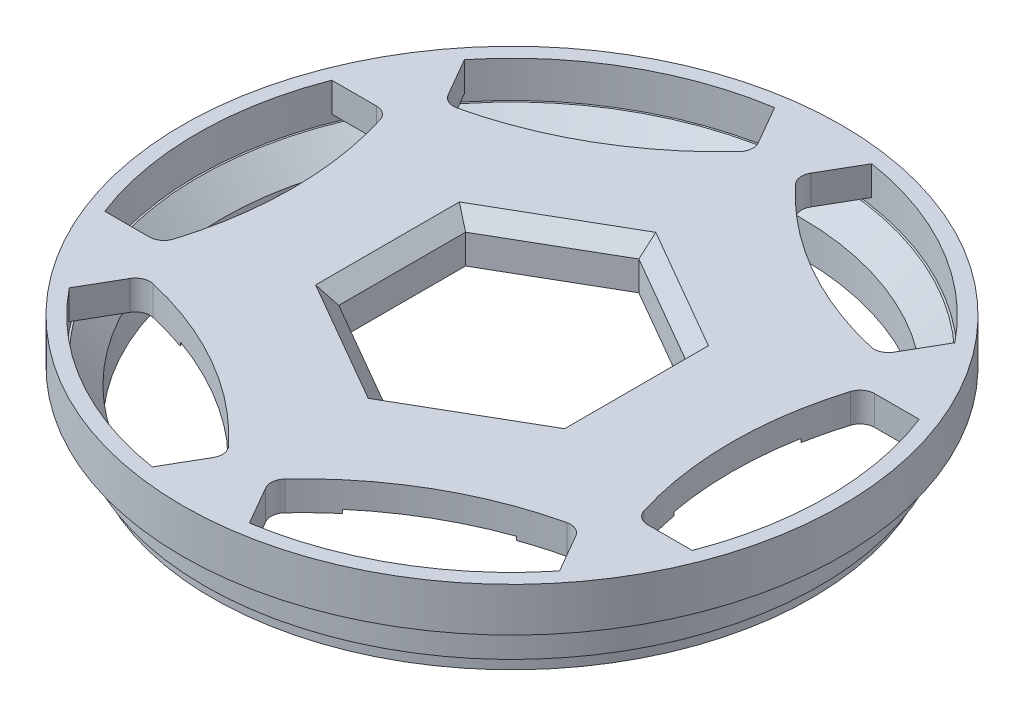
SolidWorks part; units mm, degrees
ref_plane "Ebene vorne" through (0, 0, 0) normal (0, 0, 1) x (1, 0, 0)
ref_plane "Ebene oben" through (0, 0, 0) normal (0, 1, 0) x (1, 0, 0)
ref_plane "Ebene rechts" through (0, 0, 0) normal (1, 0, 0) x (0, 0, -1)
sketch "Skizze1" plane through (0, 0, 0) normal (0, 1, 0) x (1, 0, 0)
  circle A0 centre (0, 0) radius 44
  dimension "D1" = 88
extrude "Aufsatz-Linear austragen1" add sketch "Skizze1" along normal blind 4
sketch "Skizze2" plane through (0, 4, 0) normal (0, 1, 0) x (1, 0, 0)
  line L0 (-32.5715, 15.5) -> (-71.0776, 15.5)
  line L1 (-32.5715, -15.5) -> (-71.0776, -15.5)
  line L2 (-71.0776, 15.5) -> (-71.0776, -15.5)
  circle A0 centre (-78, 0) radius 48
  circle M2 centre (0, 0) radius 44
  dimension "D1" = 78
  dimension "D2" = 96
  dimension "D3" = 31
  dimension "D4" = 15.5
extrude "Schnitt-Linear austragen2" cut sketch "Skizze2" against normal blind 10 contours L1 A0 L0 M2 region at (-36.9648, 4, 0)
sketch "Skizze4" plane through (0, 4, 0) normal (0, 1, 0) x (1, 0, 0)
  circle A0 centre (0, 0) radius 21.0071
pattern_circular "Kreismuster1" count 6 over 360 about axis through (0, 0, 0) along (0, 1, 0) of "Schnitt-Linear austragen2"
sketch "Skizze3" plane through (0, 0, 0) normal (0, -1, 0) x (1, 0, 0)
  line L1 (15, 8.6603) -> (0, 17.3205)
  line L2 (0, 17.3205) -> (-15, 8.6603)
  line L3 (-15, 8.6603) -> (-15, -8.6603)
  line L4 (-15, -8.6603) -> (0, -17.3205)
  line L5 (0, -17.3205) -> (15, -8.6603)
  line L6 (15, -8.6603) -> (15, 8.6603)
  circle A0 centre (0, 0) radius 15 construction
extrude "Schnitt-Linear austragen3" cut sketch "Skizze3" against normal blind 10 and the other way blind 4
fillet "Verrundung1" radius 2 12 edges at (-32.5715, 2, 15.5) (-2.8623, 2, 35.9577) (2.8623, 2, 35.9577) (29.7091, 2, 20.4577) (32.5715, 2, 15.5) (32.5715, 2, -15.5) (29.7091, 2, -20.4577) (2.8623, 2, -35.9577) (-2.8623, 2, -35.9577) (-29.7091, 2, -20.4577) (-32.5715, 2, -15.5) (-29.7091, 2, 20.4577)
sketch "Skizze5" plane through (13.4234, 0, 7.75) normal (-0.866, 0, -0.5) x (-0.5, 0, 0.866)
  line L0 (-34.0256, 0) -> (-41.1795, 0) construction
  circle A0 centre (-39, 0) radius 1.6
sketch "Skizze6" plane through (0, 0, -15.5) normal (0, 0, 1) x (1, 0, 0)
  line L0 (34.0256, 0) -> (41.1795, 0) construction
  circle A0 centre (39, 0) radius 1.6
sketch "Skizze7" plane through (0, 0, 0) normal (0, -1, 0) x (1, 0, 0)
  circle A0 centre (0, 0) radius 32
extrude "Schnitt-Linear austragen7" cut sketch "Skizze7" against normal blind 0.5
sketch "Skizze8" plane through (0, 4, 0) normal (0, 1, 0) x (1, 0, 0)
  circle A0 centre (0, 0) radius 45
  circle A1 centre (0, 0) radius 43
extrude "Aufsatz-Linear austragen2" add sketch "Skizze8" against normal blind 5
sketch "Skizze9" plane through (0, -1, 0) normal (0, -1, 0) x (1, 0, 0)
  circle A0 centre (0, 0) radius 45
  circle A1 centre (0, 0) radius 39.5
extrude "Aufsatz-Linear austragen3" add sketch "Skizze9" along normal blind 8 separate body
extrude "Aufsatz-Linear austragen8" add sketch "Skizze4" against normal blind 6
chamfer "Fase1" distance 3.25 angle 45 1 edges at (0, -1, -39.5)
sketch "Skizze10" plane through (0, -9, 0) normal (0, -1, 0) x (1, 0, 0)
  circle A0 centre (0, 0) radius 42
  circle A1 centre (0, 0) radius 50
extrude "Schnitt-Linear austragen9" cut sketch "Skizze10" against normal blind 7 contours A1 | A0
sketch "Skizze11" plane through (0, -9, 0) normal (0, -1, 0) x (1, 0, 0)
  circle A0 centre (0, 0) radius 40.9
  circle A1 centre (-1.9486, 1.7726) radius 50
extrude "Schnitt-Linear austragen10" cut sketch "Skizze11" against normal blind 2
extrude "Schnitt-Linear austragen11" cut sketch "Skizze3<3>" against normal blind 6 and the other way blind 6
sketch "Skizze3<3>" plane through (0, 0, 0) normal (0, -1, 0) x (1, 0, 0) same geometry as "Skizze3"
chamfer "Fase3" distance 2 angle 45 1 edges at (0, -2, 21.0071)
chamfer "Fase5" distance 2 angle 45 6 edges at (-7.5, 4, 12.9904) (7.5, 4, 12.9904) (15, 4, 0) (7.5, 4, -12.9904) (-7.5, 4, -12.9904) (-15, 4, 0)
